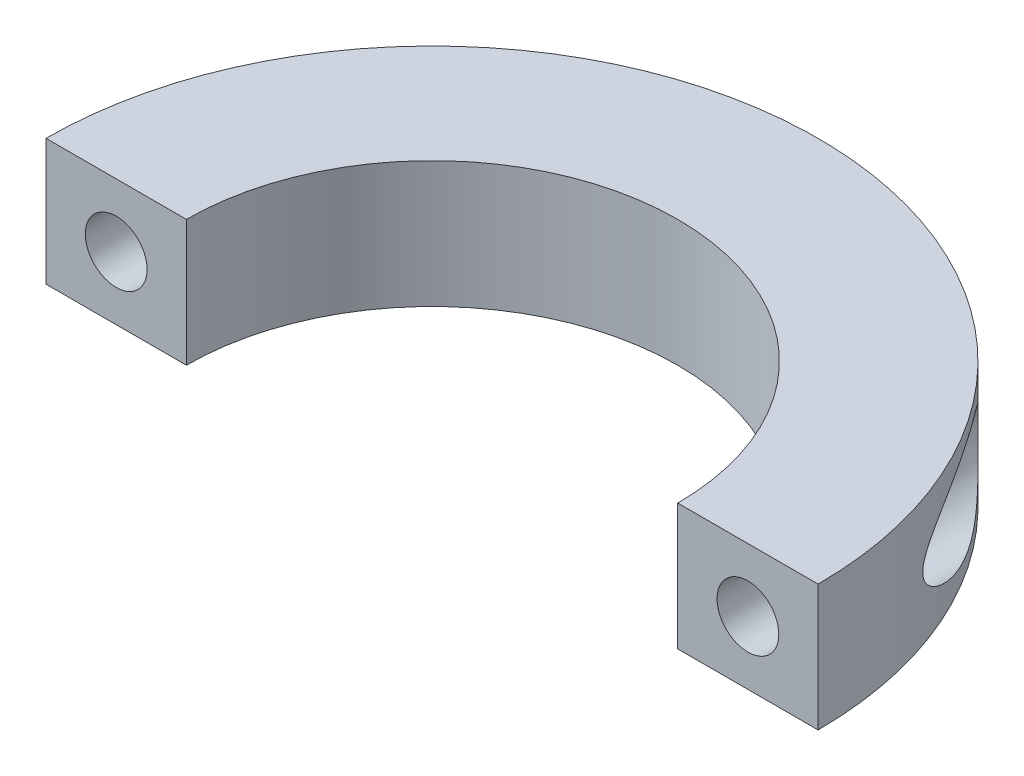
SolidWorks part; units mm, degrees
ref_plane "Front Plane" through (0, 0, 0) normal (0, 0, 1) x (1, 0, 0)
ref_plane "Top Plane" through (0, 0, 0) normal (0, 1, 0) x (1, 0, 0)
ref_plane "Right Plane" through (0, 0, 0) normal (1, 0, 0) x (0, 0, -1)
sketch "Sketch1" plane through (0, 0, 0) normal (0, 1, 0) x (1, 0, 0)
  line L0 (-25.1828, 0) -> (30.5526, 0) construction
  line L1 (-27.5, 0) -> (-17.5, 0)
  line L2 (17.5, 0) -> (27.5, 0)
  arc A0 (27.5, 0) -> (-27.5, 0) centre (0, 0) ccw
  arc A1 (17.5, 0) -> (-17.5, 0) centre (0, 0) ccw
  dimension "D1" = 17.5
  dimension "D2" = 27.5
extrude "Boss-Extrude1" add sketch "Sketch1" along normal blind 4.5 and the other way blind 4.5
sketch "Sketch2" plane through (0, 0, 0) normal (0, 0, 1) x (1, 0, 0)
  line L0 (0, 10.378) -> (0, -13.9925) construction
  point P8 (-22.5, 0)
  point P9 (22.5, 0)
  dimension "D1" = 22.5
  dimension "D2" = 22.5
sketch "Sketch5" plane through (0, 4.5, 0) normal (0, 1, 0) x (1, 0, 0)
  line L0 (-21.7417, 0) -> (21.6322, 0) construction
  line L1 (-27.5, 0) -> (-17.5, 0) construction
  line L2 (17.5, 0) -> (27.5, 0) construction
  line L3 (-15.5, 0) -> (-15, 0)
  line L4 (15, 0) -> (15.5, 0)
  line L6 (-17.5, 0) -> (-17, 0)
  line L8 (17, 0) -> (17.5, 0)
  arc A0 (15.5, 0) -> (-15.5, 0) centre (0, 0) ccw
  arc A1 (15, 0) -> (-15, 0) centre (0, 0) ccw
  arc A2 (17, 0) -> (-17, 0) centre (0, 0) ccw
  arc A3 (17.5, 0) -> (-17.5, 0) centre (0, 0) ccw
  dimension "D1" = 0.5
  dimension "D3" = 0.5
  dimension "D2" = 15
  dimension "D4" = 17
hole_wizard "Ø4.4 (4.4) Diameter Hole1" positions "3DSketch1" profile "Sketch6" hole size "Ø4.4" standard "ANSI Metric" end condition through all
sketch3d "3DSketch1"
  point P0 (22.5, 0, 0)
  point P3 (-22.5, 0, 0)
sketch "Sketch6" plane through (22.5, 0, 0) normal (1, 0, 0) x (0, -1, 0)
  line L0 (0, 0) -> (0, 27.5)
  line L1 (0, 27.5) -> (2.2, 27.5)
  line L2 (2.2, 27.5) -> (2.2, 0)
  line L5 (2.2, 0) -> (0, 0)
  line L11 (0, -6.35) -> (0, 107.95) construction
  dimension "Thru Hole Dia." = 4.4
  dimension "Thru Hole Depth" = 27.5
sketch "Sketch7" plane through (0, 0, 0) normal (0, 0, 1) x (1, 0, 0)
  circle A0 centre (-22.5, 0) radius 3.5
  circle A1 centre (22.5, 0) radius 3.5
  dimension "D1" = 7
  dimension "D2" = 7
extrude "Cut-Extrude1" cut sketch "Sketch7" against normal blind 18 from offset 8 offset against normal yes
